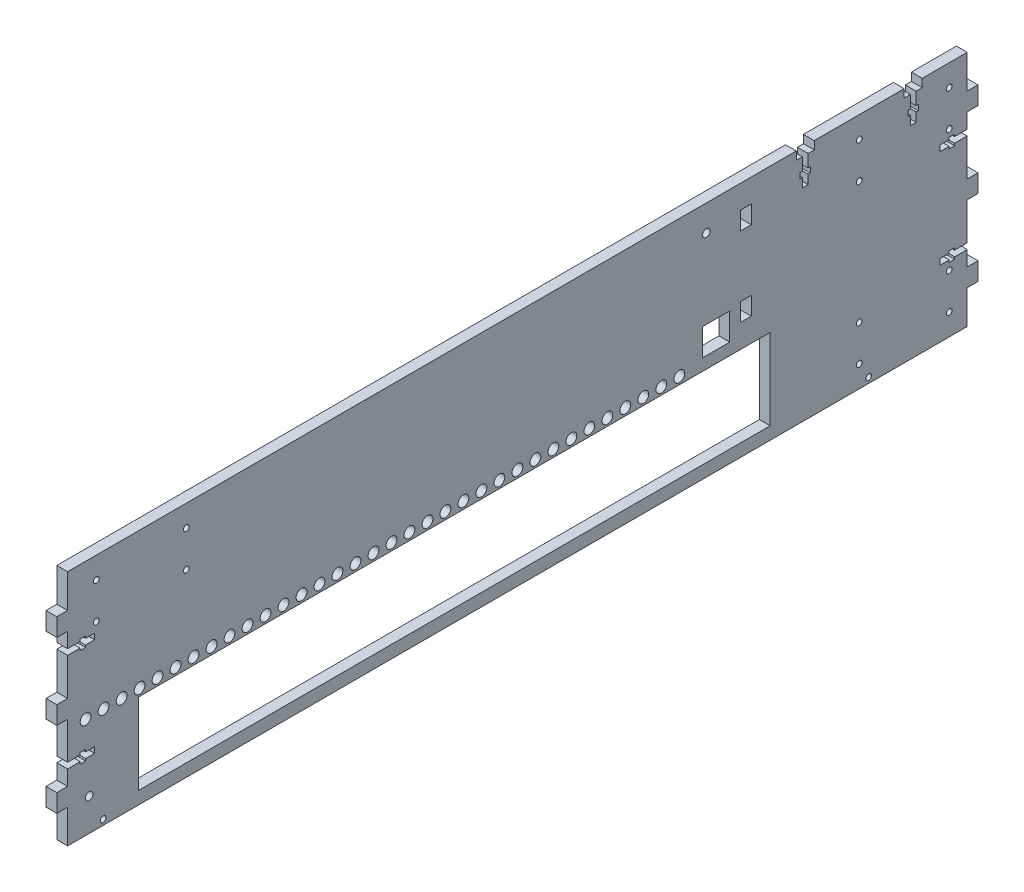
SolidWorks part; units mm, degrees
ref_plane "Front Plane" through (0, 0, 0) normal (0, 0, 1) x (1, 0, 0)
ref_plane "Top Plane" through (0, 0, 0) normal (0, 1, 0) x (1, 0, 0)
ref_plane "Right Plane" through (0, 0, 0) normal (1, 0, 0) x (0, 0, -1)
sketch "Sketch1" plane through (0, 0, 0) normal (1, 0, 0) x (0, 0, -1)
  line L1 (-250, -66) -> (250, -66)
  line L2 (-250, -66) -> (-250, 66)
  line L3 (-250, 66) -> (250, 66)
  line L4 (250, -66) -> (250, 66)
  line L5 (-250, -66) -> (250, 66) construction
  line L6 (-250, 66) -> (250, -66) construction
  point P0 (0, 0)
  dimension "D1" = 132
  dimension "D2" = 500
extrude "Boss-Extrude1" add sketch "Sketch1" along normal blind 6
sketch "Sketch4" plane through (0, 0, 250) normal (0, 0, 1) x (1, 0, 0)
  line L0 (0, 66) -> (0, -66) construction
  line L1 (0, 47.3321) -> (6, 47.3321)
  line L2 (0, 47.3321) -> (0, 37.3321)
  line L3 (0, 37.3321) -> (6, 37.3321)
  line L4 (6, 47.3321) -> (6, 37.3321)
  line L5 (6, 66) -> (6, -66) construction
  line L6 (0, 37.3321) -> (6, 37.3321) construction
  line L7 (0, -66) -> (0, 66) construction
  line L8 (6, 47.3321) -> (0, 47.3321) construction
  line L9 (0, -5) -> (6, -5) construction
  line L10 (0, -5) -> (6, -5)
  line L11 (0, -5) -> (0, 5)
  line L12 (0, 5) -> (6, 5)
  line L13 (6, -5) -> (6, 5)
  line L14 (6, -66) -> (6, 66) construction
  line L15 (6, 5) -> (0, 5) construction
  line L16 (6, -37.3321) -> (0, -37.3321) construction
  line L17 (0, -47.3321) -> (6, -47.3321)
  line L18 (0, -47.3321) -> (0, -37.3321)
  line L19 (0, -37.3321) -> (6, -37.3321)
  line L20 (6, -47.3321) -> (6, -37.3321)
  line L21 (0, -47.3321) -> (6, -47.3321) construction
extrude "Boss-Extrude2" add sketch "Sketch4" along normal blind 6
sketch "Sketch5" plane through (0, 0, 0) normal (-1, 0, 0) x (0, 0, 1)
  line L1 (250, 28.9321) -> (250, 25.7321) construction
  line L3 (250, 28.9321) -> (250, 25.7321) construction
  line L4 (250, -25.7321) -> (250, -28.9321) construction
  line L5 (250, -25.7321) -> (250, -28.9321) construction
  line L6 (250, 27.3321) -> (235, 27.3321) construction
  line L7 (250, -27.3321) -> (235, -27.3321) construction
  line L8 (250, -25.7321) -> (243, -25.7321)
  line L9 (250, 28.9321) -> (243, 28.9321)
  line L10 (250, -28.9321) -> (243, -28.9321)
  line L11 (250, 25.7321) -> (243, 25.7321)
  line L12 (250, -25.7321) -> (250, -28.9321)
  line L13 (235, -25.7321) -> (235, -28.9321)
  line L14 (250, 28.9321) -> (250, 25.7321)
  line L15 (235, 28.9321) -> (235, 25.7321)
  line L16 (240, 25.7321) -> (235, 25.7321)
  line L17 (243, 24.5321) -> (240, 24.5321)
  line L18 (243, 24.5321) -> (243, 25.7321)
  line L19 (243, 30.1321) -> (240, 30.1321)
  line L20 (240, 24.5321) -> (240, 25.7321)
  line L21 (243, 24.5321) -> (240, 30.1321) construction
  line L22 (243, 30.1321) -> (240, 24.5321) construction
  line L23 (243, -30.1321) -> (240, -30.1321)
  line L24 (243, -30.1321) -> (243, -28.9321)
  line L25 (243, -24.5321) -> (240, -24.5321)
  line L26 (240, -30.1321) -> (240, -28.9321)
  line L27 (243, -30.1321) -> (240, -24.5321) construction
  line L28 (243, -24.5321) -> (240, -30.1321) construction
  line L29 (250, 25.7321) -> (235, 25.7321) construction
  line L30 (243, 28.9321) -> (243, 30.1321)
  line L31 (240, 28.9321) -> (235, 28.9321)
  line L32 (250, 28.9321) -> (235, 28.9321) construction
  line L33 (240, 28.9321) -> (240, 30.1321)
  line L34 (240, -25.7321) -> (235, -25.7321)
  line L35 (250, -25.7321) -> (235, -25.7321) construction
  line L36 (240, -25.7321) -> (240, -24.5321)
  line L37 (240, -28.9321) -> (235, -28.9321)
  line L38 (250, -28.9321) -> (235, -28.9321) construction
  line L39 (243, -25.7321) -> (243, -24.5321)
  point P20 (241.5, 27.3321)
  point P25 (241.5, -27.3321)
  line M35 (250, -37.3321) -> (250, -5)
  line M39 (250, 5) -> (250, 37.3321)
  dimension "D3" = 1.6
  dimension "D4" = 7
  dimension "D5" = 3
  dimension "D6" = 5.6
  dimension "D1" = 15
  dimension "D7" = 7
  dimension "D8" = 3
  dimension "D9" = 5.6
  dimension "D2" = 1.6
extrude "Cut-Extrude3" cut sketch "Sketch5" against normal up to next contours L12 | L8 L39 L25 L36 L34 L13 L37 L26 L23 L24 L10 M35 | L33 L31 L15 L16 L20 L17 L18 L11 L9 L30 L19 M39 region at (0, -27.3321, 242.3696) region at (0, 27.3321, 242.3696)
sketch "Sketch6" plane through (0, 0, -250) normal (0, 0, -1) x (-1, 0, 0)
  line L0 (0, 47.3321) -> (0, 37.3321) construction
  line L1 (0, 37.3321) -> (-6, 37.3321) construction
  line L2 (-6, 37.3321) -> (-6, 47.3321) construction
  line L3 (-6, 47.3321) -> (0, 47.3321) construction
  line L4 (0, 5) -> (0, -5) construction
  line L5 (0, -5) -> (-6, -5) construction
  line L6 (-6, -5) -> (-6, 5) construction
  line L7 (-6, 5) -> (0, 5) construction
  line L8 (0, -37.3321) -> (0, -47.3321) construction
  line L9 (0, -47.3321) -> (-6, -47.3321) construction
  line L10 (-6, -47.3321) -> (-6, -37.3321) construction
  line L11 (-6, -37.3321) -> (0, -37.3321) construction
  line L12 (0, 47.3321) -> (0, 37.3321)
  line L13 (0, 37.3321) -> (-6, 37.3321)
  line L14 (-6, 37.3321) -> (-6, 47.3321)
  line L15 (-6, 47.3321) -> (0, 47.3321)
  line L16 (0, 5) -> (0, -5)
  line L17 (0, -5) -> (-6, -5)
  line L18 (-6, -5) -> (-6, 5)
  line L19 (-6, 5) -> (0, 5)
  line L20 (0, -37.3321) -> (0, -47.3321)
  line L21 (0, -47.3321) -> (-6, -47.3321)
  line L22 (-6, -47.3321) -> (-6, -37.3321)
  line L23 (-6, -37.3321) -> (0, -37.3321)
extrude "Boss-Extrude3" add sketch "Sketch6" along normal blind 6
sketch "Sketch7" plane through (0, 0, 0) normal (-1, 0, 0) x (0, 0, 1)
  line L0 (243, 25.7321) -> (250, 25.7321) construction
  line L2 (243, 25.7321) -> (243, 24.5321) construction
  line L3 (240, 24.5321) -> (243, 24.5321) construction
  line L4 (240, 25.7321) -> (240, 24.5321) construction
  line L5 (235, 25.7321) -> (240, 25.7321) construction
  line L6 (235, 25.7321) -> (235, 28.9321) construction
  line L7 (235, 28.9321) -> (240, 28.9321) construction
  line L8 (240, 30.1321) -> (240, 28.9321) construction
  line L9 (240, 30.1321) -> (243, 30.1321) construction
  line L10 (243, 30.1321) -> (243, 28.9321) construction
  line L11 (243, 28.9321) -> (250, 28.9321) construction
  line L12 (243, 25.7321) -> (250, 25.7321) construction
  line L13 (243, 25.7321) -> (243, 24.5321) construction
  line L14 (240, 24.5321) -> (243, 24.5321) construction
  line L15 (240, 25.7321) -> (240, 24.5321) construction
  line L16 (235, 25.7321) -> (240, 25.7321) construction
  line L17 (235, 25.7321) -> (235, 28.9321) construction
  line L18 (235, 28.9321) -> (240, 28.9321) construction
  line L19 (240, 30.1321) -> (240, 28.9321) construction
  line L20 (240, 30.1321) -> (243, 30.1321) construction
  line L21 (243, 30.1321) -> (243, 28.9321) construction
  line L22 (243, 28.9321) -> (250, 28.9321) construction
  line L23 (235, -28.9321) -> (240, -28.9321) construction
  line L24 (240, -28.9321) -> (240, -30.1321) construction
  line L25 (240, -30.1321) -> (243, -30.1321) construction
  line L26 (243, -28.9321) -> (243, -30.1321) construction
  line L27 (243, -28.9321) -> (250, -28.9321) construction
  line L28 (243, -25.7321) -> (250, -25.7321) construction
  line L29 (243, -24.5321) -> (243, -25.7321) construction
  line L30 (240, -24.5321) -> (243, -24.5321) construction
  line L31 (240, -24.5321) -> (240, -25.7321) construction
  line L32 (235, -25.7321) -> (240, -25.7321) construction
  line L33 (235, -28.9321) -> (235, -25.7321) construction
  line L34 (235, -28.9321) -> (240, -28.9321) construction
  line L35 (240, -28.9321) -> (240, -30.1321) construction
  line L36 (240, -30.1321) -> (243, -30.1321) construction
  line L37 (243, -28.9321) -> (243, -30.1321) construction
  line L38 (243, -28.9321) -> (250, -28.9321) construction
  line L39 (243, -25.7321) -> (250, -25.7321) construction
  line L40 (243, -24.5321) -> (243, -25.7321) construction
  line L41 (240, -24.5321) -> (243, -24.5321) construction
  line L42 (240, -24.5321) -> (240, -25.7321) construction
  line L43 (235, -25.7321) -> (240, -25.7321) construction
  line L44 (235, -28.9321) -> (235, -25.7321) construction
  line L45 (0, 0) -> (0, 57.5645) construction
  line L46 (-235, -28.9321) -> (-235, -25.7321)
  line L47 (-235, -25.7321) -> (-240, -25.7321)
  line L48 (-240, -24.5321) -> (-240, -25.7321)
  line L49 (-240, -24.5321) -> (-243, -24.5321)
  line L50 (-243, -24.5321) -> (-243, -25.7321)
  line L51 (-243, -25.7321) -> (-250, -25.7321)
  line L52 (-243, -28.9321) -> (-250, -28.9321)
  line L53 (-243, -28.9321) -> (-243, -30.1321)
  line L54 (-240, -30.1321) -> (-243, -30.1321)
  line L55 (-240, -28.9321) -> (-240, -30.1321)
  line L56 (-235, -28.9321) -> (-240, -28.9321)
  line L57 (-243, 28.9321) -> (-250, 28.9321)
  line L58 (-243, 30.1321) -> (-243, 28.9321)
  line L59 (-240, 30.1321) -> (-243, 30.1321)
  line L60 (-240, 30.1321) -> (-240, 28.9321)
  line L61 (-235, 28.9321) -> (-240, 28.9321)
  line L62 (-235, 25.7321) -> (-235, 28.9321)
  line L63 (-235, 25.7321) -> (-240, 25.7321)
  line L64 (-240, 25.7321) -> (-240, 24.5321)
  line L65 (-240, 24.5321) -> (-243, 24.5321)
  line L66 (-243, 25.7321) -> (-243, 24.5321)
  line L67 (-243, 25.7321) -> (-250, 25.7321)
  line L68 (-250, 28.9321) -> (-250, 25.7321)
  line L69 (-250, -25.7321) -> (-250, -28.9321)
extrude "Cut-Extrude4" cut sketch "Sketch7" against normal up to next
sketch "Sketch8" plane through (0, 0, 0) normal (-1, 0, 0) x (0, 0, 1)
  line L0 (210, -14.55) -> (-140, -14.55) construction
  line L1 (210, -14.55) -> (-140, -14.55) construction
  line L2 (210, -14.55) -> (210, -59) construction
  line L3 (210, -14.55) -> (210, -59) construction
  line L186 (-140, -14.55) -> (-140, -59) construction
  line L187 (-140, -59) -> (210, -59) construction
  line L188 (210.5, -14.05) -> (210.5, -59)
  line L189 (210.5, -14.05) -> (-140.5, -14.05)
  line L190 (-140.5, -14.05) -> (-140.5, -59)
  line L191 (-140.5, -59) -> (210.5, -59)
  dimension "D1" = 0.5
extrude "Cut-Extrude5" cut sketch "Sketch8" against normal up to next
sketch "Sketch11" plane through (6, 0, 0) normal (1, 0, 0) x (0, 0, -1)
  line L0 (130, 43) -> (130, 53) construction
  line L1 (130, 53) -> (124, 53) construction
  line L2 (124, 53) -> (124, 43) construction
  line L3 (124, 43) -> (130, 43) construction
  line L4 (130, -1) -> (130, 9) construction
  line L5 (130, 9) -> (124, 9) construction
  line L6 (124, 9) -> (124, -1) construction
  line L7 (124, -1) -> (130, -1) construction
  line L8 (130, 43) -> (130, 53)
  line L9 (130, 53) -> (124, 53)
  line L10 (124, 53) -> (124, 43)
  line L11 (124, 43) -> (130, 43)
  line L12 (130, -1) -> (130, 9)
  line L13 (130, 9) -> (124, 9)
  line L14 (124, 9) -> (124, -1)
  line L15 (124, -1) -> (130, -1)
extrude "Cut-Extrude8" cut sketch "Sketch11" against normal up to next
sketch "Sketch12" plane through (0, 0, 0) normal (-1, 0, 0) x (0, 0, 1)
  line L0 (-124, 53) -> (-124, 43) construction
  line L1 (-250, 66) -> (250, 66) construction
  circle A0 centre (-105, 51.5) radius 2.1
  dimension "D1" = 19
  dimension "D3" = 4.2
  dimension "D2" = 14.5
extrude "Cut-Extrude9" cut sketch "Sketch12" against normal up to next
sketch "Sketch13" plane through (0, 66, 0) normal (0, 1, 0) x (1, 0, 0)
  line L0 (6, 250) -> (6, -250) construction
  line L1 (0, 215) -> (6, 215)
  line L2 (0, 215) -> (0, 225)
  line L3 (0, 225) -> (6, 225)
  line L4 (6, 215) -> (6, 225)
  line L5 (0, 215) -> (6, 225) construction
  line L6 (0, 225) -> (6, 215) construction
  line L7 (6, 225) -> (0, 225) construction
  line L8 (6, 165) -> (0, 165) construction
  line L9 (0, 155) -> (6, 155)
  line L10 (0, 155) -> (0, 165)
  line L11 (0, 165) -> (6, 165)
  line L12 (6, 155) -> (6, 165)
  line L13 (0, 155) -> (6, 165) construction
  line L14 (0, 165) -> (6, 155) construction
  point P0 (3, 220)
  point P10 (3, 160)
extrude "Cut-Extrude10" cut sketch "Sketch13" against normal blind 4.5
sketch "Sketch14" plane through (0, 0, 0) normal (-1, 0, 0) x (0, 0, 1)
  circle A0 centre (240, -10) radius 3 construction
  circle A1 centre (240, -10) radius 3
  circle A2 centre (230, -10) radius 3
  circle A3 centre (220, -10) radius 3
  circle A4 centre (210, -10) radius 3
  circle A5 centre (200, -10) radius 3
  circle A6 centre (190, -10) radius 3
  circle A7 centre (180, -10) radius 3
  circle A8 centre (170, -10) radius 3
  circle A9 centre (160, -10) radius 3
  circle A10 centre (150, -10) radius 3
  circle A11 centre (140, -10) radius 3
  circle A12 centre (130, -10) radius 3
  circle A13 centre (120, -10) radius 3
  circle A14 centre (110, -10) radius 3
  circle A15 centre (100, -10) radius 3
  circle A16 centre (90, -10) radius 3
  circle A17 centre (80, -10) radius 3
  circle A18 centre (70, -10) radius 3
  circle A19 centre (60, -10) radius 3
  circle A20 centre (50, -10) radius 3
  circle A21 centre (40, -10) radius 3
  circle A22 centre (30, -10) radius 3
  circle A23 centre (20, -10) radius 3
  circle A24 centre (10, -10) radius 3
  circle A25 centre (0, -10) radius 3
  circle A26 centre (-10, -10) radius 3
  circle A27 centre (-20, -10) radius 3
  circle A28 centre (-30, -10) radius 3
  circle A29 centre (-40, -10) radius 3
  circle A30 centre (-50, -10) radius 3
  circle A31 centre (-60, -10) radius 3
  circle A32 centre (-70, -10) radius 3
  circle A33 centre (-80, -10) radius 3
  circle A34 centre (-90, -10) radius 3
  dimension "D1" = 34
extrude "Cut-Extrude11" cut sketch "Sketch14" against normal up to next (6 mm away)
sketch "Sketch15" plane through (6, 0, 0) normal (1, 0, 0) x (0, 0, -1)
  line L0 (160, 61.5) -> (160, 46.5) construction
  line L1 (155, 61.5) -> (165, 61.5) construction
  line L2 (220, 61.5) -> (220, 46.5) construction
  line L3 (215, 61.5) -> (225, 61.5) construction
  line L4 (160, 46.5) -> (220, 46.5) construction
  line L5 (190, 46.5) -> (190, 66) construction
  line L6 (215, 66) -> (165, 66) construction
  line L7 (158.4, 61.5) -> (158.4, 54.5)
  line L8 (161.6, 61.5) -> (161.6, 54.5)
  line L9 (158.4, 61.5) -> (161.6, 61.5)
  line L10 (158.4, 46.5) -> (161.6, 46.5)
  line L11 (161.6, 51.5) -> (162.8, 51.5)
  line L12 (157.2, 54.5) -> (158.4, 54.5)
  line L13 (157.2, 54.5) -> (157.2, 51.5)
  line L14 (157.2, 51.5) -> (158.4, 51.5)
  line L15 (162.8, 54.5) -> (162.8, 51.5)
  line L16 (157.2, 54.5) -> (162.8, 51.5) construction
  line L17 (157.2, 51.5) -> (162.8, 54.5) construction
  line L18 (161.6, 54.5) -> (162.8, 54.5)
  line L19 (158.4, 51.5) -> (158.4, 46.5)
  line L20 (158.4, 61.5) -> (158.4, 46.5) construction
  line L21 (161.6, 51.5) -> (161.6, 46.5)
  line L22 (161.6, 61.5) -> (161.6, 46.5) construction
  line L23 (222.8, 51.5) -> (217.2, 54.5) construction
  line L24 (222.8, 54.5) -> (217.2, 51.5) construction
  line L25 (220, 61.5) -> (220, 46.5) construction
  line L26 (218.4, 51.5) -> (218.4, 46.5)
  line L27 (221.6, 51.5) -> (221.6, 46.5)
  line L28 (218.4, 54.5) -> (217.2, 54.5)
  line L29 (217.2, 54.5) -> (217.2, 51.5)
  line L30 (222.8, 51.5) -> (221.6, 51.5)
  line L31 (222.8, 54.5) -> (222.8, 51.5)
  line L32 (222.8, 54.5) -> (221.6, 54.5)
  line L33 (218.4, 51.5) -> (217.2, 51.5)
  line L34 (221.6, 46.5) -> (218.4, 46.5)
  line L35 (221.6, 61.5) -> (218.4, 61.5)
  line L36 (218.4, 61.5) -> (218.4, 54.5)
  line L37 (221.6, 61.5) -> (221.6, 54.5)
  point P16 (160, 53)
  point P37 (220, 53)
  dimension "D3" = 15
  dimension "D4" = 7
  dimension "D5" = 3
  dimension "D6" = 5.6
  dimension "D1" = 1.6
  dimension "D2" = 1.6
extrude "Cut-Extrude12" cut sketch "Sketch15" against normal up to next
sketch "Sketch17" plane through (6, 0, 0) normal (1, 0, 0) x (0, 0, -1)
  circle A0 centre (-238, -48) radius 2.1 construction
  circle A1 centre (-238, -48) radius 2.1
extrude "Cut-Extrude14" cut sketch "Sketch17" against normal through all
sketch "Sketch18" plane through (6, 0, 0) normal (1, 0, 0) x (0, 0, -1)
  line L0 (-210.5, -59) -> (-250, -59) construction
  line L1 (-250, -47.3321) -> (-250, -66) construction
  line L2 (-230.25, -59) -> (-230.25, -66) construction
  line L3 (-250, -66) -> (250, -66) construction
  line L4 (140.5, -59) -> (250, -59) construction
  line L5 (250, -66) -> (250, -47.3321) construction
  line L6 (195.25, -59) -> (195.25, -66) construction
  circle A0 centre (-230.25, -63) radius 1.6
  circle A1 centre (195.25, -63) radius 1.6
  dimension "D1" = 3.2
  dimension "D2" = 3
extrude "Cut-Extrude15" cut sketch "Sketch18" against normal through all
sketch "Sketch19" plane through (6, 0, 0) normal (1, 0, 0) x (0, 0, -1)
  circle A1 centre (240, -34) radius 1.6
  circle A2 centre (240, -34) radius 1.6
  circle A3 centre (240, 54) radius 1.6
  circle A5 centre (240, 54) radius 1.6
  circle A7 centre (240, -54) radius 1.6
  circle A8 centre (240, -54) radius 1.6
  circle A11 centre (190, -54) radius 1.6
  circle A12 centre (190, -54) radius 1.6
  circle A15 centre (190, -34) radius 1.6
  circle A16 centre (190, -34) radius 1.6
  circle A24 centre (190, 34) radius 1.6
  circle A25 centre (190, 34) radius 1.6
  circle A30 centre (190, 54) radius 1.6
  circle A31 centre (190, 54) radius 1.6
  circle A32 centre (240, 34) radius 1.6
  circle A33 centre (240, 34) radius 1.6
  circle A56 centre (-184, 34) radius 1.6 construction
  circle A57 centre (-234, 34) radius 1.6 construction
  circle A58 centre (-184, 54) radius 1.6 construction
  circle A59 centre (-234, 54) radius 1.6 construction
  circle A60 centre (-184, 34) radius 1.6
  circle A61 centre (-234, 34) radius 1.6
  circle A62 centre (-184, 54) radius 1.6
  circle A63 centre (-234, 54) radius 1.6
  dimension "D1" = 0
  dimension "D2" = 0
  dimension "D5" = 0
  dimension "D7" = 0
  dimension "D9" = 0
  dimension "D12" = 0
  dimension "D15" = 0
  dimension "D16" = 0
extrude "Cut-Extrude16" cut sketch "Sketch19" against normal through all
sketch "Sketch20" plane through (6, 0, 0) normal (1, 0, 0) x (0, 0, -1)
  line L0 (-250, 22) -> (251, 22) construction
  line L1 (-250, 22) -> (251, 22) construction
  line L2 (-250, -22) -> (251, -22) construction
  line L3 (-250, -22) -> (251, -22) construction
  line L4 (118, 22) -> (118, -22) construction
  line L5 (124, 9) -> (124, -1) construction
  line L6 (118, 0) -> (103, 0) construction
  line L7 (118, 7.5) -> (103, 7.5)
  line L8 (118, -7.5) -> (103, -7.5)
  line L9 (118, 7.5) -> (118, -7.5)
  line L10 (103, 7.5) -> (103, -7.5)
  point P8 (124, 4)
  dimension "D1" = 6
  dimension "D2" = 15
  dimension "D3" = 7.5
  dimension "D4" = 7.5
extrude "Cut-Extrude17" cut sketch "Sketch20" against normal through all
